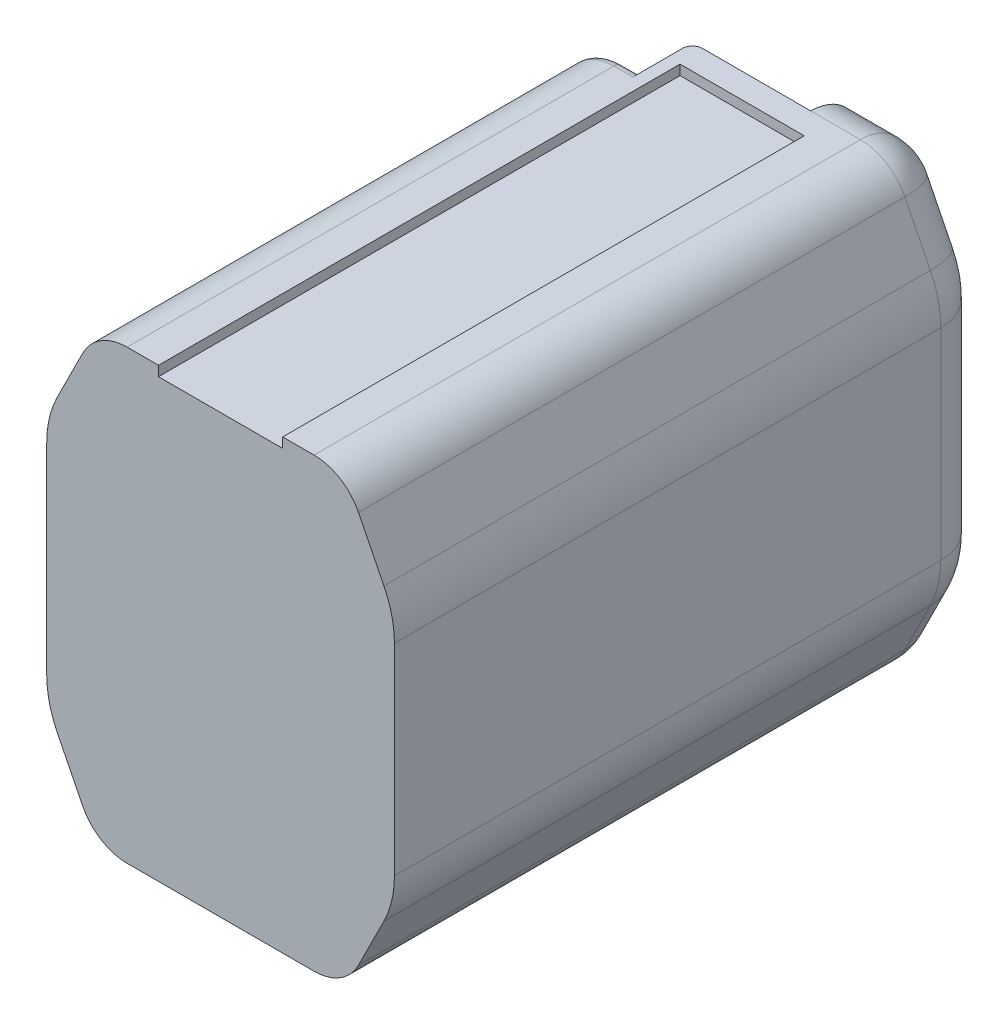
SolidWorks part; units mm, degrees
ref_plane "Front Plane" through (0, 0, 0) normal (0, 0, 1) x (1, 0, 0)
ref_plane "Top Plane" through (0, 0, 0) normal (0, 1, 0) x (1, 0, 0)
ref_plane "Right Plane" through (0, 0, 0) normal (1, 0, 0) x (0, 0, -1)
sketch "Sketch1" plane through (0, 0, 0) normal (0, 0, 1) x (1, 0, 0)
  line L0 (-32.8885, 29.2229) -> (-27.7639, 39.4721)
  line L1 (-18.8197, -45) -> (18.8197, -45)
  line L2 (-35, -20.2786) -> (-35, 20.2786)
  line L3 (-18.8197, 45) -> (18.8197, 45)
  line L4 (35, -20.2786) -> (35, 20.2786)
  line L5 (-35, -45) -> (35, 45) construction
  line L6 (-35, 45) -> (35, -45) construction
  line L7 (27.7639, 39.4721) -> (32.8885, 29.2229)
  line L8 (-32.8885, -29.2229) -> (-27.7639, -39.4721)
  line L9 (27.7639, -39.4721) -> (32.8885, -29.2229)
  arc A0 (-27.7639, -39.4721) -> (-18.8197, -45) centre (-18.8197, -35) ccw
  arc A1 (27.7639, -39.4721) -> (18.8197, -45) centre (18.8197, -35) cw
  arc A2 (27.7639, 39.4721) -> (18.8197, 45) centre (18.8197, 35) ccw
  arc A3 (-27.7639, 39.4721) -> (-18.8197, 45) centre (-18.8197, 35) cw
  arc A4 (32.8885, 29.2229) -> (35, 20.2786) centre (15, 20.2786) cw
  arc A5 (32.8885, -29.2229) -> (35, -20.2786) centre (15, -20.2786) ccw
  arc A6 (-32.8885, -29.2229) -> (-35, -20.2786) centre (-15, -20.2786) cw
  arc A7 (-32.8885, 29.2229) -> (-35, 20.2786) centre (-15, 20.2786) ccw
  point P0 (0, 0)
  point P16 (-25, -45)
  point P19 (25, -45)
  point P22 (25, 45)
  point P25 (-25, 45)
  point P28 (35, 25)
  point P31 (35, -25)
  point P34 (-35, -25)
  point P37 (-35, 25)
  dimension "D11" = 10
  dimension "D12" = 20
  dimension "D1" = 70
  dimension "D2" = 90
  dimension "D3" = 20
  dimension "D4" = 10
  dimension "D5" = 10
  dimension "D6" = 20
  dimension "D7" = 10
  dimension "D8" = 20
  dimension "D9" = 10
  dimension "D10" = 20
extrude "Boss-Extrude1" add sketch "Sketch1" against normal blind 120
sketch "Sketch2" plane through (0, 45, 0) normal (0, 1, 0) x (1, 0, 0)
  line L1 (8.8197, 120) -> (-35, 120)
  line L2 (8.8197, 120) -> (8.8197, 110)
  line L3 (8.8197, 110) -> (-15, 110)
  line L6 (-35, 100) -> (-35, 120)
  line L8 (-15, 110) -> (-15, 100)
  line L9 (-15, 100) -> (-35, 100)
  line L11 (18.8197, 120) -> (18.8197, 0) construction
  line L12 (-35, 120) -> (-35, 0) construction
  line L13 (18.8197, 120) -> (-18.8197, 120) construction
  dimension "D1" = 10
  dimension "D2" = 10
  dimension "D3" = 20
  dimension "D5" = 10
extrude "Cut-Extrude2" cut sketch "Sketch2" against normal through all
fillet "Fillet3" radius 10 9 edges at (13.8197, -45, -120) (24.077, -43.5065, -120) (30.3262, -34.3475, -120) (34.465, -24.8737, -120) (35, 0, -120) (34.465, 24.8737, -120) (30.3262, 34.3475, -120) (24.077, 43.5065, -120) (13.8197, 45, -120)
fillet "Fillet4" radius 2 9 edges at (-16.9098, -45, -100) (-24.077, -43.5065, -100) (-30.3262, -34.3475, -100) (-34.465, -24.8737, -100) (-35, 0, -100) (-34.465, 24.8737, -100) (-30.3262, 34.3475, -100) (-24.077, 43.5065, -100) (-16.9098, 45, -100)
fillet "Fillet5" radius 2 1 edges at (-15, 0, -110)
sketch "Sketch3" plane through (0, 45, 0) normal (0, 1, 0) x (1, 0, 0)
  line L1 (12.5, 0) -> (-12.5, 0)
  line L2 (12.5, 0) -> (12.5, 105)
  line L3 (12.5, 105) -> (-12.5, 105)
  line L4 (-12.5, 0) -> (-12.5, 105)
  line L8 (18.8197, 0) -> (-18.8197, 0) construction
  dimension "D1" = 25
  dimension "D2" = 12.5
  dimension "D3" = 105
extrude "Cut-Extrude3" cut sketch "Sketch3" against normal blind 2
sketch "Sketch4" plane through (-35, 0, 0) normal (-1, 0, 0) x (0, 0, 1)
  line L0 (0, 20.2786) -> (0, -20.2786) construction
  line L1 (-10, 25) -> (-60, 25)
  line L2 (-10, 25) -> (-10, -25)
  line L3 (-10, -25) -> (-60, -25)
  line L4 (-60, 25) -> (-60, -25)
  dimension "D1" = 10
  dimension "D2" = 25
  dimension "D3" = 25
  dimension "D4" = 50
extrude "Cut-Extrude5" cut sketch "Sketch4" against normal blind 5
fillet "Fillet6" radius 5 4 edges at (-32.2174, -25, -60) (-32.2174, -25, -10) (-32.2174, 25, -10) (-32.2174, 25, -60)
fillet "Fillet8" radius 2.5 12 edges at (-35, -20.1394, -10.0019) (-35, -20.1394, -59.9981) (-35, 20.1394, -59.9981) (-34.4347, 25, -35) (-35, 20.1394, -10.0019) (-34.7722, 23.2889, -58.7661) (-35, 0, -60) (-34.6614, -23.9433, -58.0742) (-34.4347, -25, -35) (-34.7722, -23.2889, -11.2339) (-34.6614, 23.9433, -11.9258) (-35, 0, -10)
